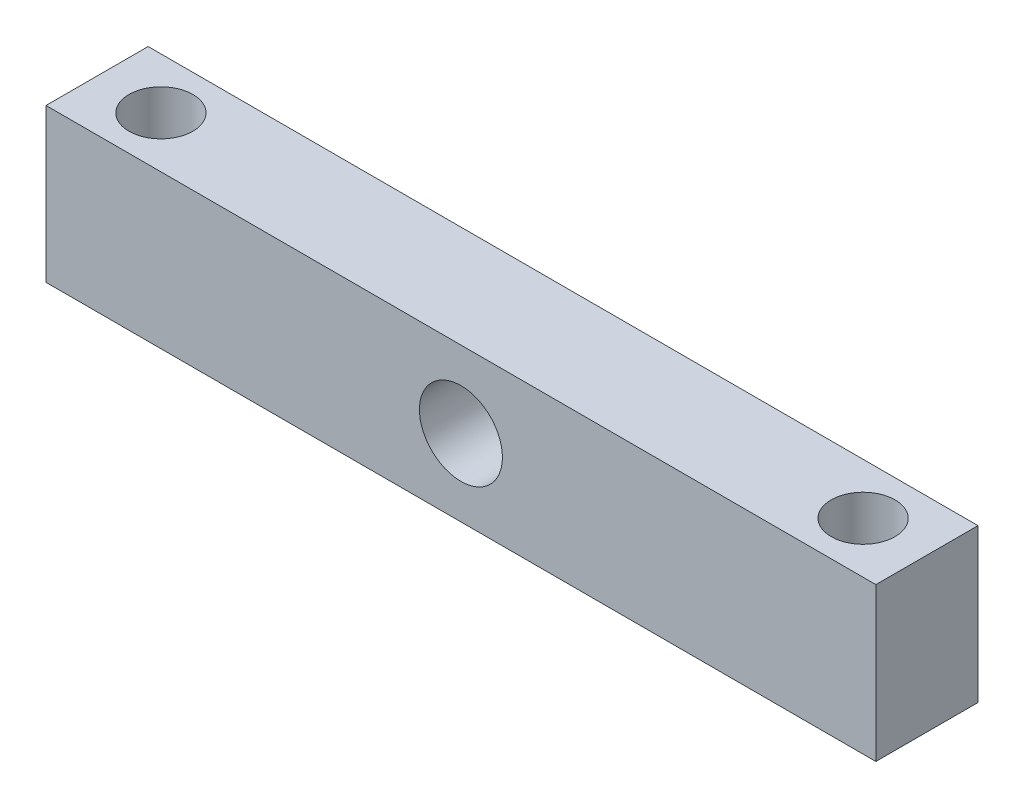
SolidWorks part; units mm, degrees
ref_plane "Front Plane" through (0, 0, 0) normal (0, 0, 1) x (1, 0, 0)
ref_plane "Top Plane" through (0, 0, 0) normal (0, 1, 0) x (1, 0, 0)
ref_plane "Right Plane" through (0, 0, 0) normal (1, 0, 0) x (0, 0, -1)
sketch "Sketch2" plane through (0, 0, 0) normal (0, 1, 0) x (1, 0, 0)
  line L0 (-27.5, 0) -> (27.5, 0) construction
  line L5 (-32.5, -4) -> (32.5, -4)
  line L6 (-32.5, -4) -> (-32.5, 4)
  line L7 (-32.5, 4) -> (32.5, 4)
  line L8 (32.5, -4) -> (32.5, 4)
  line L9 (-32.5, -4) -> (32.5, 4) construction
  line L10 (-32.5, 4) -> (32.5, -4) construction
  circle A0 centre (-27.5, 0) radius 2.5
  circle A1 centre (27.5, 0) radius 2.5
  point P0 (0, 0)
  point P10 (0, 0)
  dimension "D4" = 5
  dimension "D1" = 8
  dimension "D2" = 65
  dimension "D3" = 55
extrude "Boss-Extrude1" add sketch "Sketch2" along normal blind 12
sketch "Sketch3" plane through (0, 0, 4) normal (0, 0, 1) x (1, 0, 0)
  line L0 (32.5, 12) -> (32.5, 0) construction
  circle A0 centre (0, 6) radius 3.25
  point P2 (0, 0)
  point P6 (0, 0)
  point P7 (32.5, 6)
  dimension "D1" = 6.5
extrude "Cut-Extrude1" cut sketch "Sketch3" against normal through all
